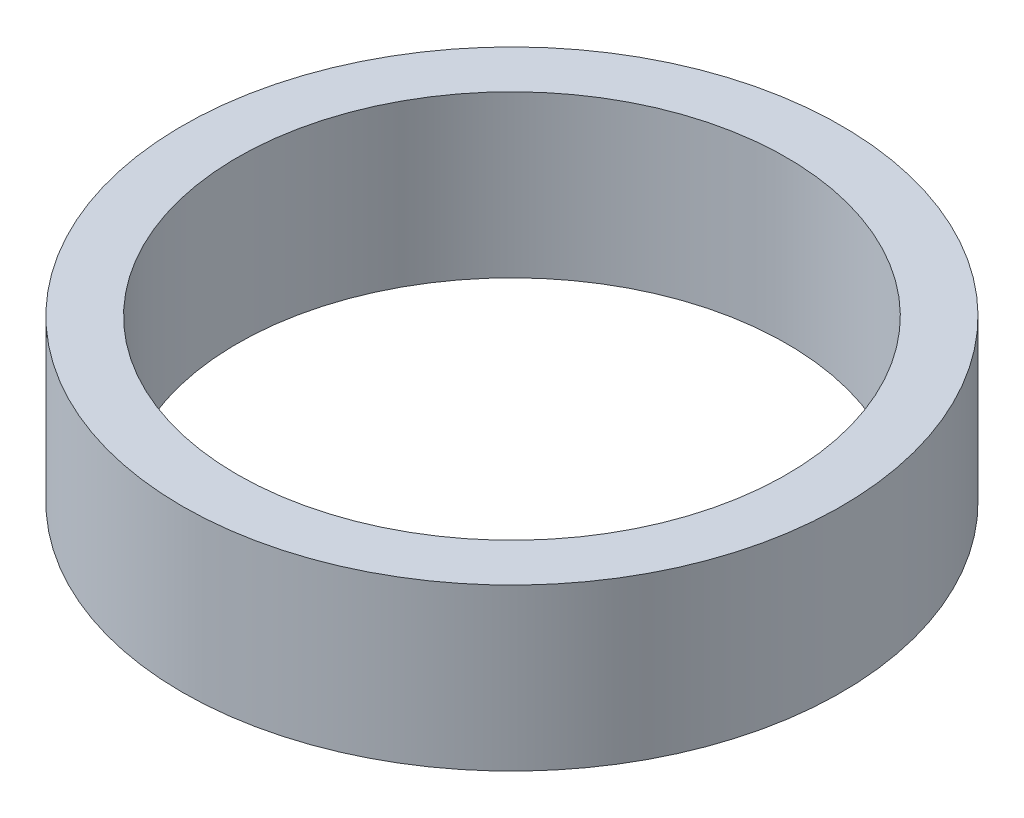
SolidWorks part; units mm, degrees
ref_plane "Front Plane" through (0, 0, 0) normal (0, 0, 1) x (1, 0, 0)
ref_plane "Top Plane" through (0, 0, 0) normal (0, 1, 0) x (1, 0, 0)
ref_plane "Right Plane" through (0, 0, 0) normal (1, 0, 0) x (0, 0, -1)
sketch "Sketch1" plane through (0, 0, 0) normal (0, 1, 0) x (1, 0, 0)
  circle A0 centre (0, 0) radius 45
  dimension "FLANGE_OD" = 90
extrude "Boss-Extrude1" add sketch "Sketch1" along normal blind 22
sketch "Sketch2" plane through (0, 0, 0) normal (0, 1, 0) x (1, 0, 0)
  circle A0 centre (0, 0) radius 37.5
  dimension "BORE_D" = 75
extrude "Cut-Extrude1" cut sketch "Sketch2" along normal through all
sketch "Sketch3" plane through (0, 22, 0) normal (0, 1, 0) x (1, 0, 0)
  circle A0 centre (0, 0) radius 20.8219 construction
  circle A1 centre (-20.8219, 0) radius 1.5
  dimension "BOLT_D" = 3
  dimension "BOLT_PCD" = 41.6438
extrude "Cut-Extrude2" cut sketch "Sketch3" against normal blind 18.8912 rebuild error yes
pattern_circular "CirPattern1" count 6 over 360 rebuild error yes
